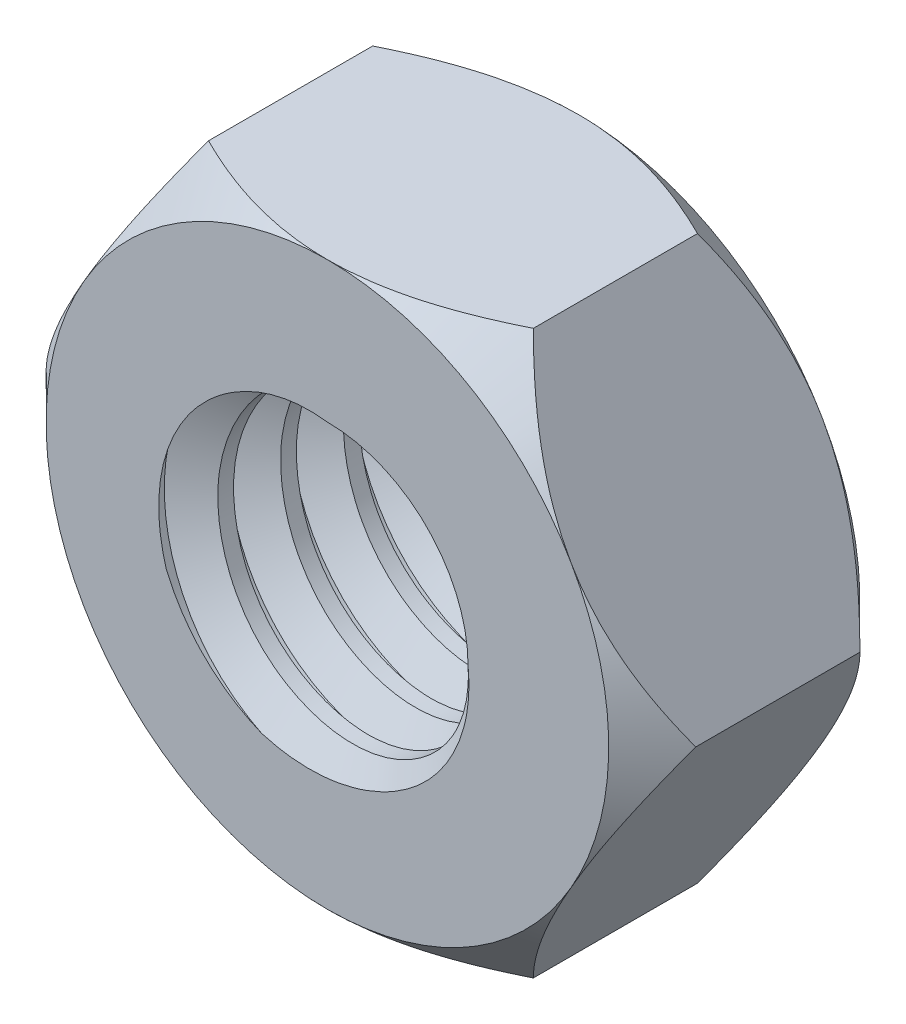
SolidWorks part; units mm, degrees
ref_plane "Front Plane" through (0, 0, 0) normal (0, 0, 1) x (1, 0, 0)
ref_plane "Top Plane" through (0, 0, 0) normal (0, 1, 0) x (1, 0, 0)
ref_plane "Right Plane" through (0, 0, 0) normal (1, 0, 0) x (0, 0, -1)
sketch "Sketch1" plane through (0, 0, 0) normal (0, 0, 1) x (1, 0, 0)
  line L1 (-26.8378, 23.2125) -> (-28.4802, 26.0573)
  line L2 (-28.4802, 26.0573) -> (-31.7651, 26.0573)
  line L3 (-31.7651, 26.0573) -> (-33.4075, 23.2125)
  line L4 (-33.4075, 23.2125) -> (-31.7651, 20.3677)
  line L5 (-31.7651, 20.3677) -> (-28.4802, 20.3677)
  line L6 (-28.4802, 20.3677) -> (-26.8378, 23.2125)
  circle A2 centre (-30.1227, 23.2125) radius 2.8448 construction
extrude "Boss-Extrude1" add sketch "Sketch1" along normal blind 2.54 contours L1 L2 L3 L4 L5 L6
sketch "Sketch4" plane through (0, 0, 2.54) normal (0, 0, 1) x (1, 0, 0)
  circle A0 centre (-30.1227, 23.2125) radius 1.4224
extrude "Cut-Extrude1" cut sketch "Sketch4" against normal through all
thread "Thread1" pitch 0.635 method cut trim with start face yes trim with end face yes profile "Thread Profile1" start angle 0, offset 1.27, length 12.7, pitch 0.635, diameter 2.8448
ref_plane "Plane1" through (-28.7003, 23.2125, -1.27) normal (0, -1, 0) x (1, 0, 0)
sketch "Thread Profile1" plane through (-28.7003, 23.2125, -1.27) normal (0, -1, 0) x (1, 0, 0)
  line L0 (0, 0) -> (0, 0.635) construction
  line L1 (0, 0) -> (0.3437, 0.1984)
  line L2 (0.3437, 0.1984) -> (0.3437, 0.2778)
  line L3 (0.3437, 0.2778) -> (0, 0.4762)
  line L4 (0.3437, 0.2381) -> (0, 0.2381) construction
  line L11 (0, 0) -> (0, 0.4762)
  point P2 (0, 0)
  dimension "Pitch" = 0.635
  dimension "Profile_Angle" = 60
  dimension "Profile_Land" = 0.0794
  dimension "Profile_Height" = 0.3437
sketch "Sketch10" plane through (0, 0, 0) normal (0, 0, -1) x (-1, 0, 0)
  circle A0 centre (30.1227, 23.2125) radius 2.8448
extrude "Cut-Extrude2" cut sketch "Sketch10" against normal blind 2.54 draft 45 flip side to cut
sketch "Sketch11" plane through (0, 0, 2.54) normal (0, 0, 1) x (1, 0, 0)
  circle A0 centre (-30.1227, 23.2125) radius 2.8448
extrude "Cut-Extrude3" cut sketch "Sketch11" against normal blind 2.54 draft 45 flip side to cut
